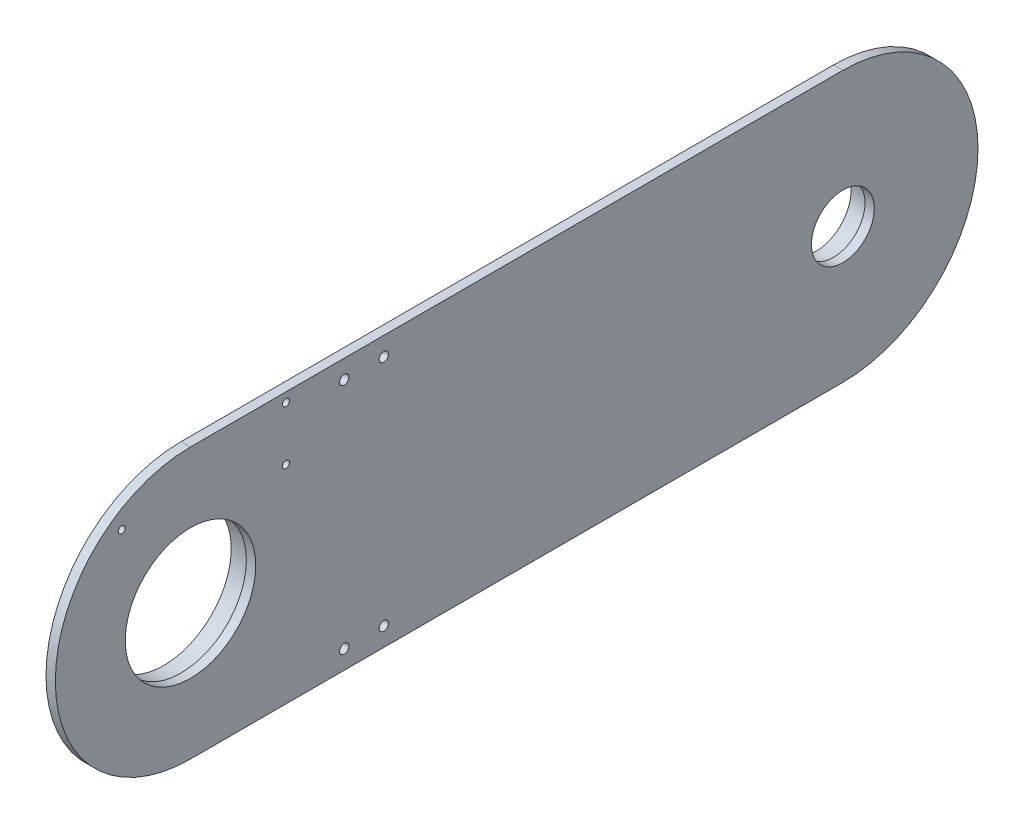
SolidWorks part; units mm, degrees
material "Zoltek Panex 33"
ref_plane "Front Plane" through (0, 0, 0) normal (0, 0, 1) x (1, 0, 0)
ref_plane "Top Plane" through (0, 0, 0) normal (0, 1, 0) x (1, 0, 0)
ref_plane "Right Plane" through (0, 0, 0) normal (1, 0, 0) x (0, 0, -1)
sketch "Sketch1" plane through (0, 0, 0) normal (1, 0, 0) x (0, 0, -1)
  line L0 (0, 0) -> (280, 0) construction
  line L1 (0, 58) -> (280, 58)
  line L2 (0, -58) -> (280, -58)
  arc A0 (0, 58) -> (0, -58) centre (0, 0) ccw
  arc A1 (280, -58) -> (280, 58) centre (280, 0) ccw
  circle A2 centre (0, 0) radius 28
  circle A3 centre (280, 0) radius 13.5
  point P3 (140, 0)
  dimension "D2" = 58
  dimension "D3" = 56
  dimension "D4" = 27
  dimension "D1" = 280
extrude "Boss-Extrude1" add sketch "Sketch1" along normal blind 4
ref_plane "Plane1" through (-7.5, 0, 0) normal (-1, 0, 0) x (0, 0, 1)
sketch "Sketch2" plane through (-7.5, 0, 0) normal (-1, 0, 0) x (0, 0, 1)
  line L0 (-140, 58) -> (-140, -58) construction
  line L1 (-280, 58) -> (0, 58) construction
  line L2 (0, -58) -> (-280, -58) construction
  circle A0 centre (0, 0) radius 29
  circle A1 centre (0, 0) radius 34
  circle A2 centre (-280, 0) radius 15
  circle A3 centre (-280, 0) radius 20
  dimension "D1" = 58
  dimension "D2" = 68
  dimension "D3" = 30
  dimension "D4" = 40
extrude "Boss-Extrude2" add sketch "Sketch2" against normal up to surface (7.5 mm away) up to face at (0, 0, -140)
chamfer "Chamfer1" distance 8 angle 45 2 edges at (0, 0, -34) (0, 0, -300)
sketch "Sketch3" plane through (0, 0, 0) normal (-1, 0, 0) x (0, 0, 1)
  line L0 (0, 58) -> (-73, 58) construction
  line L1 (-280, 58) -> (0, 58) construction
  line L2 (-73, 58) -> (-73, -58) construction
  line L3 (0, -58) -> (-280, -58) construction
  line L4 (-73, 58) -> (-76, 58) construction
  line L5 (-76, 58) -> (-76, -58) construction
  line L6 (-69.0931, 53.5) -> (-66, 53.5) construction
  line L7 (-66, 46.5) -> (-69.0931, 46.5) construction
  line L8 (-66, 50) -> (-73, 50) construction
  line L9 (-73, 55.8533) -> (-73, 44.1467) construction
  line L10 (-73, 0) -> (-99.886, 0) construction
  line L11 (-74.5, 58) -> (-74.5, 37.4458) construction
  arc A0 (-69.0931, 53.5) -> (-73, 55.8533) centre (-69.0931, 57.9197) cw construction
  arc A1 (-66, 53.5) -> (-66, 46.5) centre (-66, 50) cw construction
  arc A2 (-69.0931, 46.5) -> (-73, 44.1467) centre (-69.0931, 42.0803) ccw construction
  circle A3 centre (-66, 50) radius 2
  circle A4 centre (-66, -50) radius 2
  circle A5 centre (-83, -50) radius 2
  circle A6 centre (-83, 50) radius 2
  dimension "D3" = 4
  dimension "D1" = 73
  dimension "D2" = 3
  dimension "D4" = 7
  dimension "D5" = 8
  dimension "D6" = 7
extrude "Cut-Extrude1" cut sketch "Sketch3" against normal through all contours A3 | A4 | A6 | A5
sketch "Sketch4" plane through (4, 0, 0) normal (1, 0, 0) x (0, 0, -1)
  line L0 (0, 58) -> (73, 58) construction
  line L1 (280, 58) -> (0, 58) construction
  line L2 (73, 58) -> (73, 42) construction
  line L3 (73, 42) -> (-29.5, 42) construction
  line L4 (73, 58) -> (73, 54) construction
  line L5 (73, 54) -> (41, 54) construction
  line L6 (41, 54) -> (41, 31) construction
  circle A0 centre (-29.5, 42) radius 1.5
  circle A1 centre (41, 54) radius 1.5
  circle A2 centre (41, 31) radius 1.5
  dimension "D4" = 3
  dimension "D8" = 3
  dimension "D9" = 3
  dimension "D1" = 73
  dimension "D2" = 16
  dimension "D3" = 102.5
  dimension "D5" = 4
  dimension "D6" = 32
  dimension "D7" = 23
extrude "Cut-Extrude2" cut sketch "Sketch4" against normal through all
equation "\"mini-flipper-shaft-diameter\"= 26mm"
equation "\"mini-shaft-ring-groove-diam\"= 7.8mm"
equation "\"mini-shaft-ring-groove-width\"= 1mm"
equation "\"dtCoverPlate-DistFrom-GearCent\"= 73mm"
equation "\"wormGearShaft-L\"= \"dtCoverPlate-DistFrom-GearCent\" - 27.75 + 3.75"
equation "\"D1@Sketch3\"=\"dtCoverPlate-DistFrom-GearCent\""
